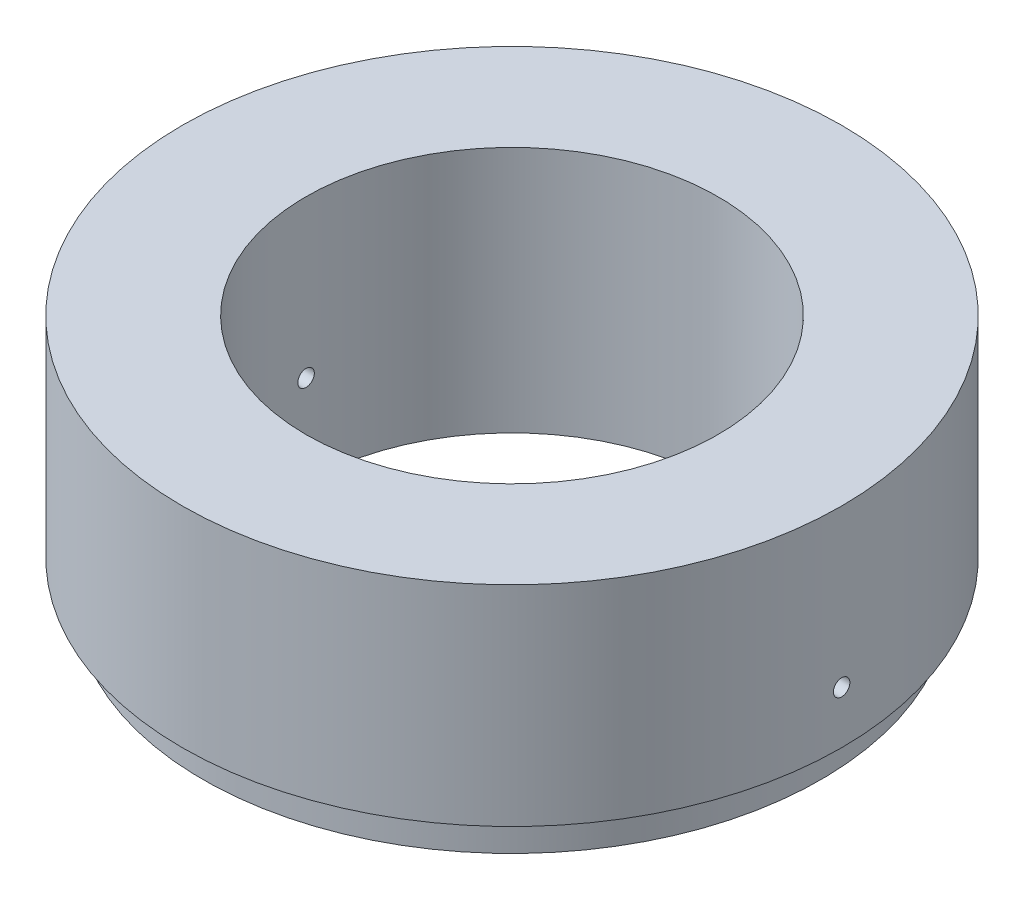
SolidWorks part; units mm, degrees
material "C (Graphite)"
ref_plane "Front Plane" through (0, 0, 0) normal (0, 0, 1) x (1, 0, 0)
ref_plane "Top Plane" through (0, 0, 0) normal (0, 1, 0) x (1, 0, 0)
ref_plane "Right Plane" through (0, 0, 0) normal (1, 0, 0) x (0, 0, -1)
sketch "Sketch1" plane through (0, 0, 0) normal (0, 1, 0) x (1, 0, 0)
  circle A0 centre (0, 0) radius 40
  circle A1 centre (0, 0) radius 25
  dimension "D1" = 80
  dimension "D2" = 50
extrude "Boss-Extrude1" add sketch "Sketch1" along normal blind 30
sketch "Sketch2" plane through (0, 0, 0) normal (0, -1, 0) x (1, 0, 0)
  circle A0 centre (0, 0) radius 37.5
  circle A1 centre (0, 0) radius 40
  dimension "D1" = 75
  dimension "D2" = 80
extrude "Cut-Extrude1" cut sketch "Sketch2" against normal blind 4.6
sketch "Sketch3" plane through (0, 0, 0) normal (1, 0, 0) x (0, 0, -1)
  line L0 (40, 30) -> (-40, 30) construction
  circle A0 centre (0, 10.95) radius 1
  dimension "D1" = 2
  dimension "D2" = 19.05
extrude "Cut-Extrude2" cut sketch "Sketch3" against normal through all both and the other way through all
